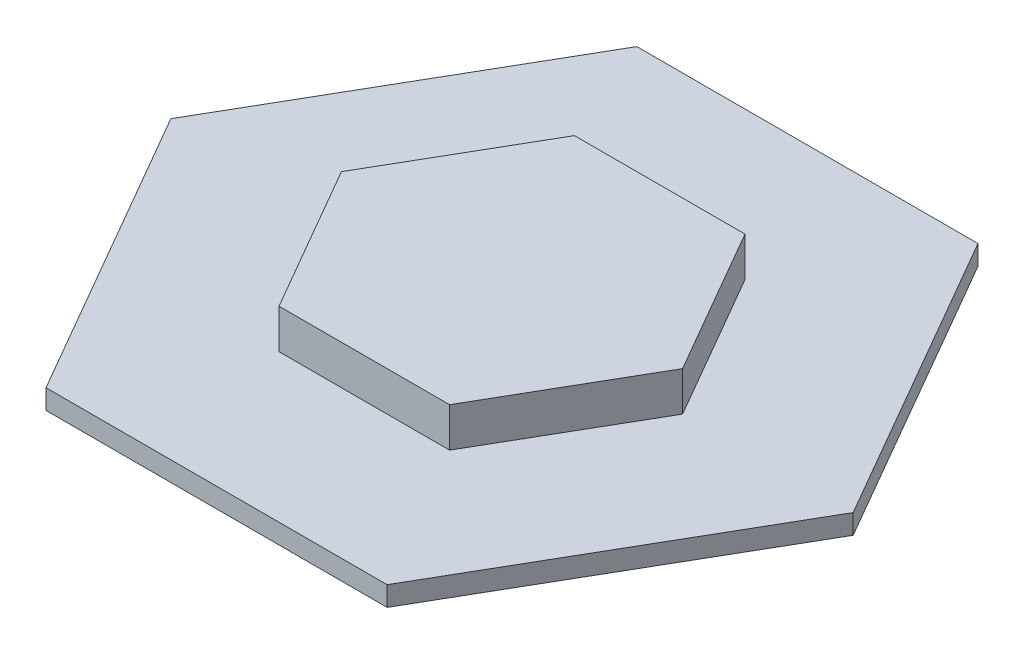
SolidWorks part; units mm, degrees
ref_plane "Front Plane" through (0, 0, 0) normal (0, 0, 1) x (1, 0, 0)
ref_plane "Top Plane" through (0, 0, 0) normal (0, 1, 0) x (1, 0, 0)
ref_plane "Right Plane" through (0, 0, 0) normal (1, 0, 0) x (0, 0, -1)
sketch "Sketch2" plane through (0, 0, 0) normal (0, 1, 0) x (1, 0, 0)
  line L1 (17.3205, 0) -> (8.6603, 15)
  line L2 (8.6603, 15) -> (-8.6603, 15)
  line L3 (-8.6603, 15) -> (-17.3205, 0)
  line L4 (-17.3205, 0) -> (-8.6603, -15)
  line L5 (-8.6603, -15) -> (8.6603, -15)
  line L6 (8.6603, -15) -> (17.3205, 0)
  line L7 (8.6603, 0) -> (4.3301, 7.5)
  line L8 (4.3301, 7.5) -> (-4.3301, 7.5)
  line L9 (-4.3301, 7.5) -> (-8.6603, 0)
  line L10 (-8.6603, 0) -> (-4.3301, -7.5)
  line L11 (-4.3301, -7.5) -> (4.3301, -7.5)
  line L12 (4.3301, -7.5) -> (8.6603, 0)
  circle A0 centre (0, 0) radius 15 construction
  circle A1 centre (0, 0) radius 7.5 construction
  point P1 (0, 0)
  point P17 (0, 0)
  point P18 (0, 0)
  point P19 (0, 0)
  point P20 (0, 0)
  point P21 (0, 0)
  point P22 (0, 0)
  point P23 (0, 0)
  point P24 (0, 0)
  point P25 (0, 0)
  point P26 (0, 0)
  point P27 (0, 0)
  point P28 (17.3205, 0)
  dimension "D1" = 30
  dimension "D2" = 15
  dimension "D3" = 8.6603
extrude "Boss-Extrude1" add sketch "Sketch2" along normal blind 1
extrude "Boss-Extrude2" add sketch "Sketch2<2>" along normal blind 3 contours L11 L12 L7 L8 L9 L10 region at (0, 0, 0)
sketch "Sketch2<2>" plane through (0, 0, 0) normal (0, 1, 0) x (1, 0, 0) same geometry as "Sketch2"
